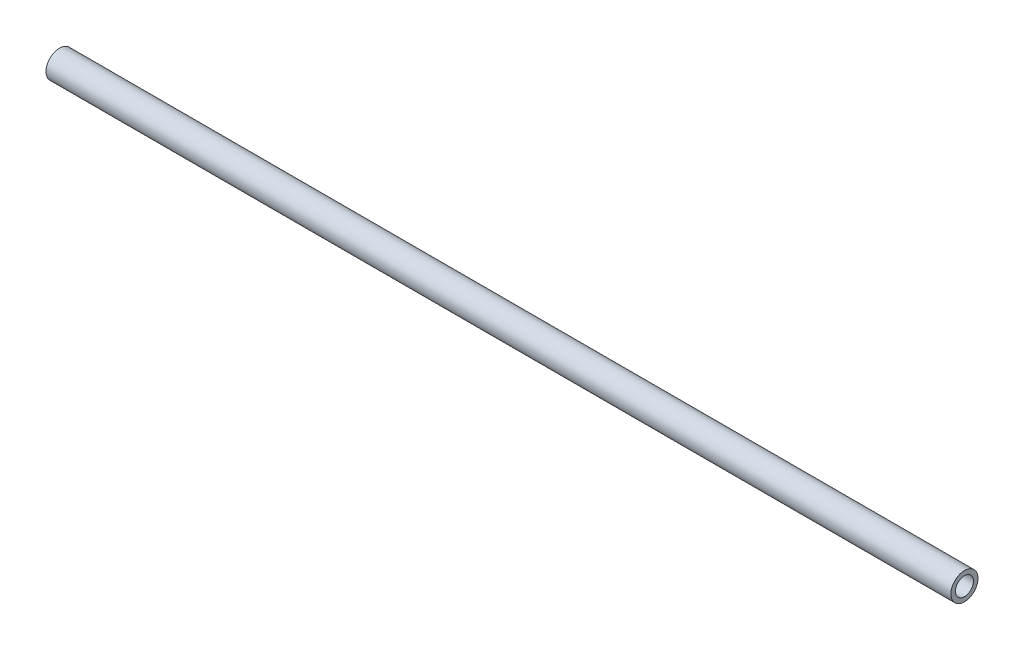
SolidWorks part; units mm, degrees
material "NEOPRENE"
ref_plane "Front Plane" through (0, 0, 0) normal (0, 0, 1) x (1, 0, 0)
ref_plane "Top Plane" through (0, 0, 0) normal (0, 1, 0) x (1, 0, 0)
ref_plane "Right Plane" through (0, 0, 0) normal (1, 0, 0) x (0, 0, -1)
sketch "Sketch1" plane through (0, 0, 0) normal (1, 0, 0) x (0, 0, -1)
  circle A0 centre (0, 0) radius 6.35
  circle A1 centre (0, 0) radius 9.525
  dimension "D1" = 12.7
  dimension "D2" = 19.05
extrude "Boss-Extrude1" add sketch "Sketch1" along normal blind 635
